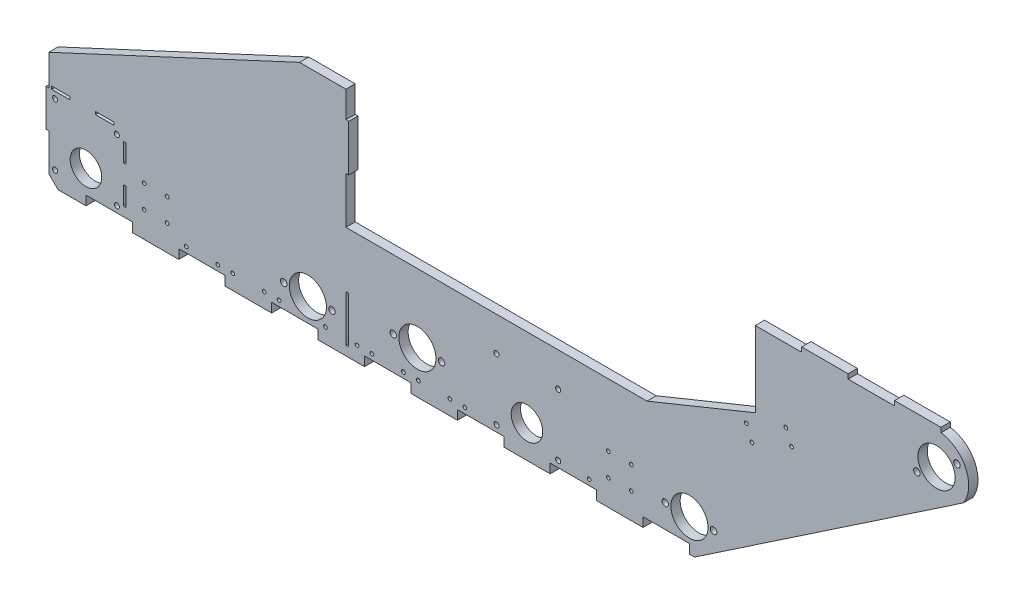
SolidWorks part; units mm, degrees
material "아크릴(내충격성)"
ref_plane "정면" through (0, 0, 0) normal (0, 0, 1) x (1, 0, 0)
ref_plane "윗면" through (0, 0, 0) normal (0, 1, 0) x (1, 0, 0)
ref_plane "우측면" through (0, 0, 0) normal (1, 0, 0) x (0, 0, -1)
sketch "스케치1" plane through (0, 0, 0) normal (0, 0, 1) x (1, 0, 0)
  line L0 (35.3016, 38.2586) -> (35.3016, -130.1494) construction
  line L3 (5.2676, -97.6555) -> (35.3016, -97.6555)
  line L5 (-42.9653, -47.6555) -> (113.7321, -47.6555) construction
  line L6 (-13.0327, -95.9898) -> (35.3016, -47.6555) construction
  line L7 (360.3016, 61.656) -> (360.3016, -136.4824) construction
  line L10 (685.3016, -62.6555) -> (510.3016, -62.6555) construction
  line L11 (510.3016, -62.6555) -> (470.1121, -62.6555) construction
  line L12 (652.0676, -14.4224) -> (652.0676, -80.8905) construction
  line L13 (2.0676, -14.4224) -> (2.0676, -80.8905) construction
  line L14 (510.3016, -62.6555) -> (951.4227, 116.8455) construction
  line L15 (639.5932, 22.3445) -> (956.2142, 151.1839)
  line L16 (685.3016, -62.6555) -> (951.4227, 116.8455) construction
  line L17 (35.3016, -62.6555) -> (274.3016, -62.6555) construction
  line L18 (274.3016, -62.6555) -> (392.3016, -62.6555) construction
  line L19 (392.3016, -62.6555) -> (392.3016, -51.6555) construction
  line L20 (347.1794, -51.6555) -> (433.0872, -51.6555) construction
  line L22 (718.5356, -14.4224) -> (456.239, -14.4224) construction
  line L23 (-14.6984, -87.6555) -> (705.4567, -87.6555) construction
  line L24 (685.3016, -62.6555) -> (722.4102, -62.6555) construction
  line L25 (980.3852, 97.7862) -> (690.6311, -97.6555)
  line L26 (35.3016, -97.6555) -> (35.3016, -87.6555)
  line L27 (231.5316, 22.3445) -> (231.5316, -97.6555) construction
  line L28 (35.3016, -87.6555) -> (85.3016, -87.6555)
  line L29 (182.7916, 22.3445) -> (182.7916, -87.6555) construction
  line L30 (85.3016, -87.6555) -> (85.3016, -97.6555)
  line L34 (135.3016, -97.6555) -> (135.3016, -87.6555)
  line L38 (231.5316, -97.6555) -> (235.3016, -97.6555)
  line L39 (135.2976, -97.6555) -> (135.3016, -97.6555)
  line L40 (135.3016, -87.6555) -> (185.3016, -87.6555)
  line L41 (185.3016, -87.6555) -> (185.3016, -97.6555)
  line L42 (85.3056, -97.6555) -> (135.2976, -97.6555)
  line L43 (185.3016, -97.6555) -> (231.5316, -97.6555)
  line L44 (235.3016, -97.6555) -> (235.3016, -87.6555)
  line L45 (235.3016, -87.6555) -> (285.3016, -87.6555)
  line L46 (285.3016, -87.6555) -> (285.3016, -97.6555)
  line L47 (335.3016, -97.6555) -> (335.3016, -87.6555)
  line L48 (335.3016, -87.6555) -> (385.3016, -87.6555)
  line L49 (385.3016, -87.6555) -> (385.3016, -97.6555)
  line L50 (435.3016, -97.6555) -> (435.3016, -87.6555)
  line L51 (435.3016, -87.6555) -> (485.3016, -87.6555)
  line L52 (485.3016, -87.6555) -> (485.3016, -97.6555)
  line L53 (535.3016, -97.6555) -> (535.3016, -87.6555)
  line L54 (535.3016, -87.6555) -> (585.3016, -87.6555)
  line L55 (585.3016, -87.6555) -> (585.3016, -97.6555)
  line L56 (635.3016, -97.6555) -> (635.3016, -87.6555)
  line L57 (635.3016, -87.6555) -> (685.3016, -87.6555)
  line L58 (685.3016, -87.6555) -> (685.3016, -97.6555)
  line L59 (85.3016, -97.6555) -> (85.3056, -97.6555)
  line L60 (285.3016, -97.6555) -> (335.3016, -97.6555)
  line L61 (385.3016, -97.6555) -> (435.3016, -97.6555)
  line L62 (485.3016, -97.6555) -> (535.3016, -97.6555)
  line L63 (585.3016, -97.6555) -> (635.3016, -97.6555)
  line L64 (685.3016, -97.6555) -> (690.6311, -97.6555)
  line L65 (-25.5762, -81.6555) -> (758.4959, -81.6555) construction
  line L66 (110.3016, -97.6555) -> (110.3016, -39.5812) construction
  line L71 (110.3016, -57.6555) -> (92.8016, -57.6555) construction
  line L72 (110.3016, -57.6555) -> (97.9272, -45.2811) construction
  line L73 (610.3016, -97.6555) -> (610.3016, -39.5812) construction
  line L74 (610.3016, -57.6555) -> (592.8016, -57.6555) construction
  line L75 (610.3016, -57.6555) -> (597.9272, -45.2811) construction
  line L76 (-14.6984, -7.4224) -> (81.4007, -7.4224) construction
  line L77 (75.5356, -87.6555) -> (75.5356, 5.7003) construction
  line L78 (315.3016, 122.6616) -> (315.3016, 146.501)
  line L79 (-11.6984, -97.6555) -> (-11.6984, -7.4224) construction
  line L87 (315.3016, -97.6555) -> (315.3016, 22.3445) construction
  line L88 (-1.6984, -7.4224) -> (18.3016, -7.4224)
  line L89 (-1.6984, -7.4224) -> (-1.6984, -4.4224)
  line L90 (-1.6984, -4.4224) -> (18.3016, -4.4224)
  line L91 (18.3016, -7.4224) -> (18.3016, -4.4224)
  line L92 (65.5356, -7.4224) -> (45.5356, -7.4224)
  line L93 (65.5356, -7.4224) -> (65.5356, -4.4224)
  line L94 (65.5356, -4.4224) -> (45.5356, -4.4224)
  line L95 (45.5356, -7.4224) -> (45.5356, -4.4224)
  line L96 (75.5356, -17.4224) -> (78.6964, -17.4224)
  line L97 (75.5356, -17.4224) -> (75.5356, -37.4224)
  line L98 (75.5356, -37.4224) -> (78.6964, -37.4224)
  line L99 (78.6964, -17.4224) -> (78.6964, -37.4224)
  line L100 (75.5356, -77.6555) -> (78.6964, -77.6555)
  line L101 (75.5356, -77.6555) -> (75.5356, -57.6555)
  line L102 (75.5356, -57.6555) -> (78.6964, -57.6555)
  line L103 (78.6964, -77.6555) -> (78.6964, -57.6555)
  line L104 (321.0516, -97.6555) -> (321.0516, -72.2502) construction
  line L105 (315.3016, 22.3445) -> (315.3016, 151.1839) construction
  line L114 (315.3016, 151.1839) -> (956.2142, 151.1839) construction
  line L115 (315.3016, 22.3445) -> (315.3016, 72.6616)
  line L118 (315.3016, 22.3445) -> (639.5932, 22.3445)
  line L121 (315.3016, -87.6555) -> (318.3016, -87.6555)
  line L122 (315.3016, -87.6555) -> (315.3016, -37.6555)
  line L123 (315.3016, -37.6555) -> (318.3016, -37.6555)
  line L124 (318.3016, -87.6555) -> (318.3016, -37.6555)
  line L125 (315.3016, 72.6616) -> (318.3016, 72.6616)
  line L127 (315.3016, 122.6616) -> (318.3016, 122.6616)
  line L128 (318.3016, 72.6616) -> (318.3016, 122.6616)
  line L130 (315.3016, 146.501) -> (315.3016, 151.1839)
  line L131 (315.3016, 151.1839) -> (265.2997, 151.1839)
  line L132 (265.2997, 151.1839) -> (-4.7324, 25.5846)
  line L133 (-4.7324, -97.6555) -> (-4.7324, 25.5846) construction
  line L135 (-4.7324, -87.6555) -> (5.2676, -97.6555)
  line L136 (-7.7324, -97.6555) -> (-7.7324, 24.1892) construction
  line L139 (-4.7324, -87.6555) -> (-4.7324, -47.6895)
  line L140 (-4.7324, -47.6895) -> (-7.7324, -47.6895)
  line L141 (-7.7324, -47.6895) -> (-7.7324, -7.6895)
  line L142 (-7.7324, -7.6895) -> (-4.7324, -7.6895)
  line L143 (-4.7324, -7.6895) -> (-4.7324, 25.5846)
  circle A1 centre (2.0676, -80.8905) radius 2.75
  circle A5 centre (2.0676, -14.4224) radius 2.75
  circle A6 centre (68.5356, -14.4224) radius 2.75
  circle A7 centre (68.5356, -80.8905) radius 2.75
  circle A12 centre (35.3016, -62.6555) radius 17
  circle A13 centre (685.3016, -62.6555) radius 20
  circle A14 centre (951.4227, 116.8455) radius 20
  circle A15 centre (973.4042, 130.7311) radius 3.5
  circle A16 centre (930.3015, 101.6831) radius 3.5
  arc A18 (980.3852, 97.7862) -> (956.2142, 151.1839) centre (951.4227, 116.8455) ccw
  circle A22 centre (274.3016, -62.6555) radius 20
  circle A23 centre (248.3016, -62.6555) radius 3.5
  circle A24 centre (300.3016, -62.6555) radius 3.5
  circle A25 centre (392.3016, -51.6555) radius 20
  circle A26 centre (366.3016, -51.6555) radius 3.5
  circle A27 centre (418.3016, -51.6555) radius 3.5
  circle A28 centre (543.8987, -14.4224) radius 2.75
  circle A29 centre (477.4307, -14.4224) radius 2.75
  circle A30 centre (477.4307, -80.8905) radius 2.75
  circle A31 centre (543.8987, -80.8905) radius 2.75
  circle A32 centre (510.3016, -62.6555) radius 17
  circle A33 centre (659.3016, -62.6555) radius 3.5
  circle A34 centre (711.3016, -62.6555) radius 3.5
  circle A37 centre (143.3016, -81.6555) radius 2
  circle A38 centre (177.3016, -81.6555) radius 2
  circle A39 centre (193.3016, -81.6555) radius 2
  circle A40 centre (227.3016, -81.6555) radius 2
  circle A41 centre (243.3016, -81.6555) radius 2
  circle A43 centre (293.3016, -81.6555) radius 2
  circle A44 centre (327.3016, -81.6555) radius 2
  circle A45 centre (343.3016, -81.6555) radius 2
  circle A46 centre (377.3016, -81.6555) radius 2
  circle A47 centre (393.3016, -81.6555) radius 2
  circle A48 centre (427.3016, -81.6555) radius 2
  circle A49 centre (443.3016, -81.6555) radius 2
  circle A54 centre (577.3016, -81.6555) radius 2
  circle A67 centre (97.9272, -45.2811) radius 2
  circle A68 centre (122.676, -45.2811) radius 2
  circle A69 centre (122.676, -70.0298) radius 2
  circle A70 centre (97.9272, -70.0298) radius 2
  circle A72 centre (597.9272, -45.2811) radius 2
  circle A73 centre (622.676, -45.2811) radius 2
  circle A74 centre (622.676, -70.0298) radius 2
  circle A75 centre (597.9272, -70.0298) radius 2
  point P22 (28.6519, -47.9736)
  point P25 (35.3016, -47.6565)
  point P53 (730.8621, 27.095)
  dimension "D3" = 175
  dimension "D5" = 4
  dimension "D9" = 34
  dimension "D10" = 26
  dimension "D12" = 7
  dimension "D13" = 40
  dimension "D14" = 7
  dimension "D20" = 33.235
  dimension "D22" = 7
  dimension "D23" = 7
  dimension "D29" = 26
  dimension "D7" = 40
  dimension "D39" = 40
  dimension "D42" = 40
  dimension "D43" = 45
  dimension "D47" = 7
  dimension "D45" = 3
  dimension "D48" = 25
  dimension "D4" = 45
  dimension "D6" = 325
  dimension "D8" = 15
  dimension "D11" = 321
  dimension "D15" = 26
  dimension "D16" = 26
  dimension "D17" = 26
  dimension "D18" = 66.468
  dimension "D19" = 30
  dimension "D21" = 35
  dimension "D24" = 26
  dimension "D25" = 239
  dimension "D26" = 26
  dimension "D27" = 118
  dimension "D28" = 11
  dimension "D30" = 26
  dimension "D31" = 179.5009
  dimension "D32" = 10
  dimension "D33" = 16.77
  dimension "D34" = 50
  dimension "D35" = 48.74
  dimension "D37" = 7
  dimension "D38" = 6
  dimension "D40" = 49.996
  dimension "D41" = 45
  dimension "D44" = 3
  dimension "D46" = 7
  dimension "D50" = 10
  dimension "D51" = 20
  dimension "D52" = 20
  dimension "D53" = 10
  dimension "D54" = 10
  dimension "D55" = 20
  dimension "D56" = 20
  dimension "D57" = 15
  dimension "D58" = 6.25
  dimension "D59" = 8
  dimension "D60" = 3
  dimension "D61" = 50
extrude "보스-돌출1" add sketch "스케치1" along normal blind 10
sketch "스케치2" plane through (0, 0, 10) normal (0, 0, 1) x (1, 0, 0)
  line L2 (756.2142, 151.1839) -> (756.2142, 69.7999)
  line L3 (956.2142, 151.1839) -> (639.5932, 22.3445) construction
  line L4 (757.4592, 156.1839) -> (983.3519, 156.1839) construction
  line L5 (806.2142, 151.1839) -> (806.2142, 156.1839)
  line L6 (806.2142, 156.1839) -> (856.2142, 156.1839)
  line L7 (856.2142, 156.1839) -> (856.2142, 151.1839)
  line L8 (906.2142, 151.1839) -> (906.2142, 156.1839)
  line L9 (906.2142, 156.1839) -> (956.2142, 156.1839)
  line L11 (806.2142, 151.1839) -> (756.2142, 151.1839)
  line L12 (906.2142, 151.1839) -> (856.2142, 151.1839)
  line L13 (956.2142, 156.1839) -> (956.2142, 151.1839)
  line L14 (956.2142, 151.1839) -> (756.2142, 69.7999)
  line L15 (756.2142, 151.1839) -> (756.2142, 201.5102) construction
  line L16 (265.2997, 151.1839) -> (756.2142, 151.1839) construction
  dimension "D1" = 50
  dimension "D2" = 81.384
  dimension "D3" = 50
  dimension "D4" = 50
  dimension "D5" = 50
  dimension "D6" = 5
  dimension "D7" = 5
  dimension "D8" = 5
extrude "보스-돌출3" add sketch "스케치2" against normal blind 10
sketch "스케치3" plane through (0, 0, 10) normal (0, 0, 1) x (1, 0, 0)
  line L0 (491.1525, -16.4677) -> (932.5771, 163.1579) construction
  line L1 (598.2558, 2.2837) -> (833.1912, 97.8842) construction
  line L2 (642.8706, -22.7464) -> (861.9919, 66.419) construction
  line L3 (696.3835, 67.0454) -> (718.379, 12.9923) construction
  line L4 (816.7959, 116.044) -> (841.4558, 55.4431) construction
  line L5 (651.9839, 16.6759) -> (881.2925, 109.9867) construction
  line L6 (777.8935, 100.2137) -> (800.5201, 44.6094) construction
  line L7 (756.5897, 91.5447) -> (779.5403, 35.1444) construction
  line L8 (735.286, 82.8757) -> (756.6675, 30.3313) construction
  line L9 (712.1807, 23.8974) -> (847.6453, 79.021) construction
  circle A1 centre (510.3016, -62.6555) radius 50
  circle A8 centre (951.4227, 116.8455) radius 50
  circle A9 centre (746.5632, 55.1624) radius 2
  circle A10 centre (752.5938, 40.3424) radius 2
  circle A11 centre (789.1707, 72.5003) radius 2
  circle A12 centre (795.2012, 57.6803) radius 2
  dimension "D5" = 100
  dimension "D6" = 100
  dimension "D1" = 23
  dimension "D2" = 40
  dimension "D3" = 130
  dimension "D4" = 125
  dimension "D7" = 6.92
  dimension "D8" = 65
  dimension "D9" = 23
  dimension "D10" = 23
  dimension "D11" = 16
extrude "컷-돌출1" cut sketch "스케치3" against normal through all contours A10 | A9 | A11 | A12
sketch "스케치4" [suppressed] plane through (0, 0, 10) normal (0, 0, 1) x (1, 0, 0)
  line L0 (510.3016, -112.6555) -> (685.3016, -112.6555)
  line L1 (491.4561, -16.343) -> (932.5772, 163.158)
  line L2 (713.2612, -104.1073) -> (979.3823, 75.3936)
  line L3 (510.3016, -62.6555) -> (685.3016, -62.6555) construction
  line L4 (951.4227, 116.8455) -> (951.4227, -62.6555) construction
  circle A0 centre (510.3016, -62.6555) radius 50
  circle A1 centre (951.4227, 116.8455) radius 50
  circle A2 centre (685.3016, -62.6555) radius 50
  dimension "D1" = 100
  dimension "D2" = 100
  dimension "D3" = 100
